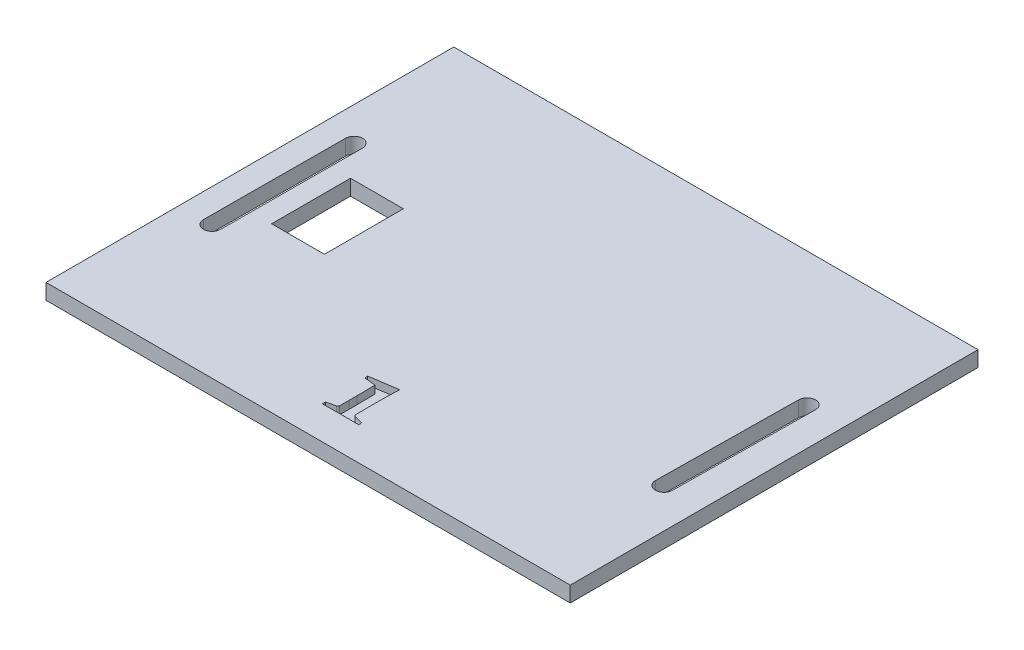
SolidWorks part; units mm, degrees
ref_plane "Front Plane" through (0, 0, 0) normal (0, 0, 1) x (1, 0, 0)
ref_plane "Top Plane" through (0, 0, 0) normal (0, 1, 0) x (1, 0, 0)
ref_plane "Right Plane" through (0, 0, 0) normal (1, 0, 0) x (0, 0, -1)
sketch "Sketch1" plane through (0, 0, 0) normal (0, 1, 0) x (1, 0, 0)
  line L1 (-42.8625, 33.3375) -> (42.8625, 33.3375)
  line L2 (-42.8625, 33.3375) -> (-42.8625, -33.3375)
  line L3 (-42.8625, -33.3375) -> (42.8625, -33.3375)
  line L4 (42.8625, 33.3375) -> (42.8625, -33.3375)
  line L5 (-42.8625, 33.3375) -> (42.8625, -33.3375) construction
  line L6 (-42.8625, -33.3375) -> (42.8625, 33.3375) construction
  line L8 (-42.8625, 15.3624) -> (-42.8625, 0.1224)
  point P0 (0, 0)
  dimension "D1" = 85.725
  dimension "D2" = 66.675
extrude "Boss-Extrude2" add sketch "Sketch1" along normal blind 2.54 contours L1 L4 L3 L2
hole_wizard "7/64 (0.10938) Diameter Slot1" positions "Sketch3" profile "Sketch4" size "7/64" standard "ANSI Inch" slot yes end condition through all
sketch "Sketch3" plane through (0, 2.54, 0) normal (0, 1, 0) x (1, 0, 0)
  line L0 (36.3915, -12.953) -> (36.7084, 12.953) construction
  point P0 (36.5499, 0)
  dimension "D1" = 25.908
sketch "Sketch4" plane through (36.5499, 2.54, 0) normal (1, 0, 0) x (0, 0, 1)
  line L0 (0, 0) -> (0, 2.54)
  line L1 (0, 2.54) -> (1.3891, 2.54)
  line L2 (1.3891, 2.54) -> (1.3891, 0)
  line L5 (1.3891, 0) -> (0, 0)
  line L11 (0, -6.35) -> (0, 107.95) construction
  dimension "Thru Hole Dia." = 2.7783
  dimension "Thru Hole Depth" = 2.54
hole_wizard "7/64 (0.10938) Diameter Slot2" positions "Sketch5" profile "Sketch6" size "7/64" standard "ANSI Inch" slot yes end condition through all
sketch "Sketch5" plane through (0, 2.54, 0) normal (0, 1, 0) x (1, 0, 0)
  line L0 (-37.5028, -12.9539) -> (-37.3843, 12.9539) construction
  point P0 (-37.4436, 0)
  point P9 (-37.4436, 0)
  dimension "D1" = 25.908
sketch "Sketch6" plane through (-37.4436, 2.54, 0) normal (1, 0, 0) x (0, 0, 1)
  line L0 (0, 0) -> (0, 2.54)
  line L1 (0, 2.54) -> (1.3891, 2.54)
  line L2 (1.3891, 2.54) -> (1.3891, 0)
  line L5 (1.3891, 0) -> (0, 0)
  line L11 (0, -6.35) -> (0, 107.95) construction
  dimension "Thru Hole Dia." = 2.7783
  dimension "Thru Hole Depth" = 2.54
sketch "Sketch7" plane through (0, 2.54, 0) normal (0, 1, 0) x (1, 0, 0)
  line L1 (-32.7182, 6.3076) -> (-24.0776, 6.3076)
  line L2 (-32.7182, 6.3076) -> (-32.7182, -6.587)
  line L3 (-32.7182, -6.587) -> (-24.0776, -6.587)
  line L4 (-24.0776, 6.3076) -> (-24.0776, -6.587)
  point P4 (-24.9315, -6.587)
extrude "Cut-Extrude1" cut sketch "Sketch7" against normal through all
sketch "Sketch8" plane through (0, 2.54, 0) normal (0, 1, 0) x (1, 0, 0)
  text T0 "1\r\n" font "Constantia" height in points 48
  point P1 (-2.8524, -27.5682)
  point P2 (-3.5843, -27.9341)
extrude "Cut-Extrude2" cut sketch "Sketch8" against normal blind 1.27
equation "\"3.00mmin\"=3"
equation "\"3.00inn\"=3"
equation "\"0.50inn\"=0.1"
